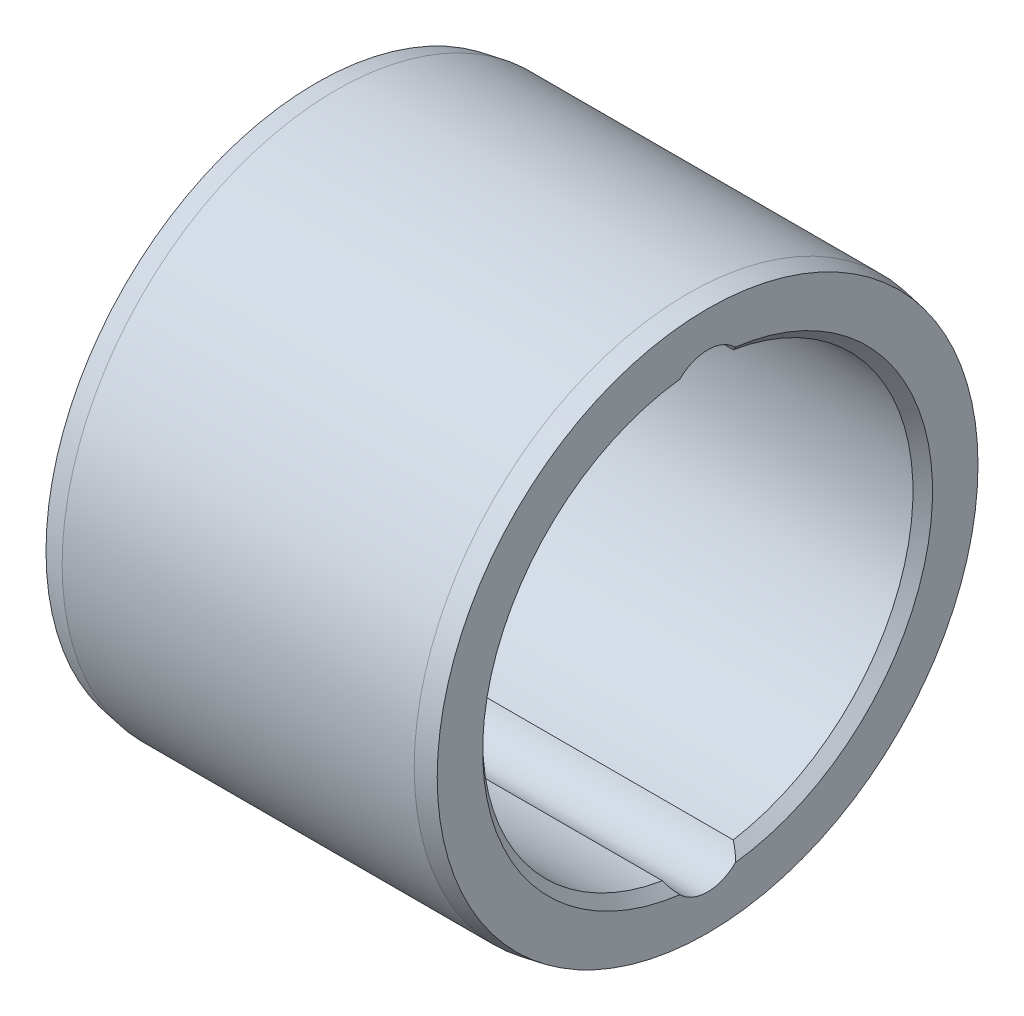
SolidWorks part; units mm, degrees
material "Алюминиевая бронза"
ref_plane "Спереди" through (0, 0, 0) normal (0, 0, 1) x (1, 0, 0)
ref_plane "Сверху" through (0, 0, 0) normal (0, 1, 0) x (1, 0, 0)
ref_plane "Справа" through (0, 0, 0) normal (1, 0, 0) x (0, 0, -1)
sketch "Эскиз1" plane through (0, 0, 0) normal (0, 0, 1) x (1, 0, 0)
  line L0 (-7.0028, 0) -> (39.6826, 0) construction
  line L1 (0, 11.5) -> (0, 13.8237)
  line L2 (0, 13.8237) -> (1, 14)
  line L3 (1, 14) -> (19, 14)
  line L4 (20, 13.8237) -> (20, 11.5)
  line L5 (19.5, 11) -> (0.5, 11)
  line L6 (19, 14) -> (20, 13.8237)
  line L7 (0.5, 11) -> (0, 11.5)
  line L8 (20, 11.5) -> (19.5, 11)
  point P3 (0, 11)
  point P8 (20, 11)
  dimension "D1" = 22
  dimension "D2" = 28
  dimension "D3" = 10
  dimension "D4" = 20
  dimension "D5" = 10
  dimension "D6" = 0.5
  dimension "D7" = 45
  dimension "D8" = 0.5
  dimension "D9" = 45
  dimension "D10" = 1
  dimension "D11" = 1
revolve "Повернуть1" add sketch "Эскиз1" angle 360 about L0
sketch "Эскиз2" plane through (20, 0, 0) normal (1, 0, 0) x (0, 0, -1)
  line L0 (0, -17.3429) -> (0, 16.985) construction
  line L1 (-16.3923, 0) -> (16.6732, 0) construction
  circle A0 centre (0, 0) radius 11 construction
  arc A1 (-1.8104, -10.85) -> (1.8104, -10.85) centre (0, 0) ccw
  arc A2 (-1.8104, 10.85) -> (1.8104, 10.85) centre (0, 10) cw
  arc A4 (-1.8104, -10.85) -> (1.8104, -10.85) centre (0, -10) ccw
  arc A5 (1.8104, 10.85) -> (-1.8104, 10.85) centre (0, 0) ccw
  dimension "D1" = 1
  dimension "D2" = 2
extrude "Вырез-Вытянуть1" cut sketch "Эскиз2" against normal offset from surface (18 mm away) 2 up to face at (0, 0, 11.5)
fillet "Скругление1" radius 1.5 2 edges at (2, 12, 0) (2, -12, 0)
